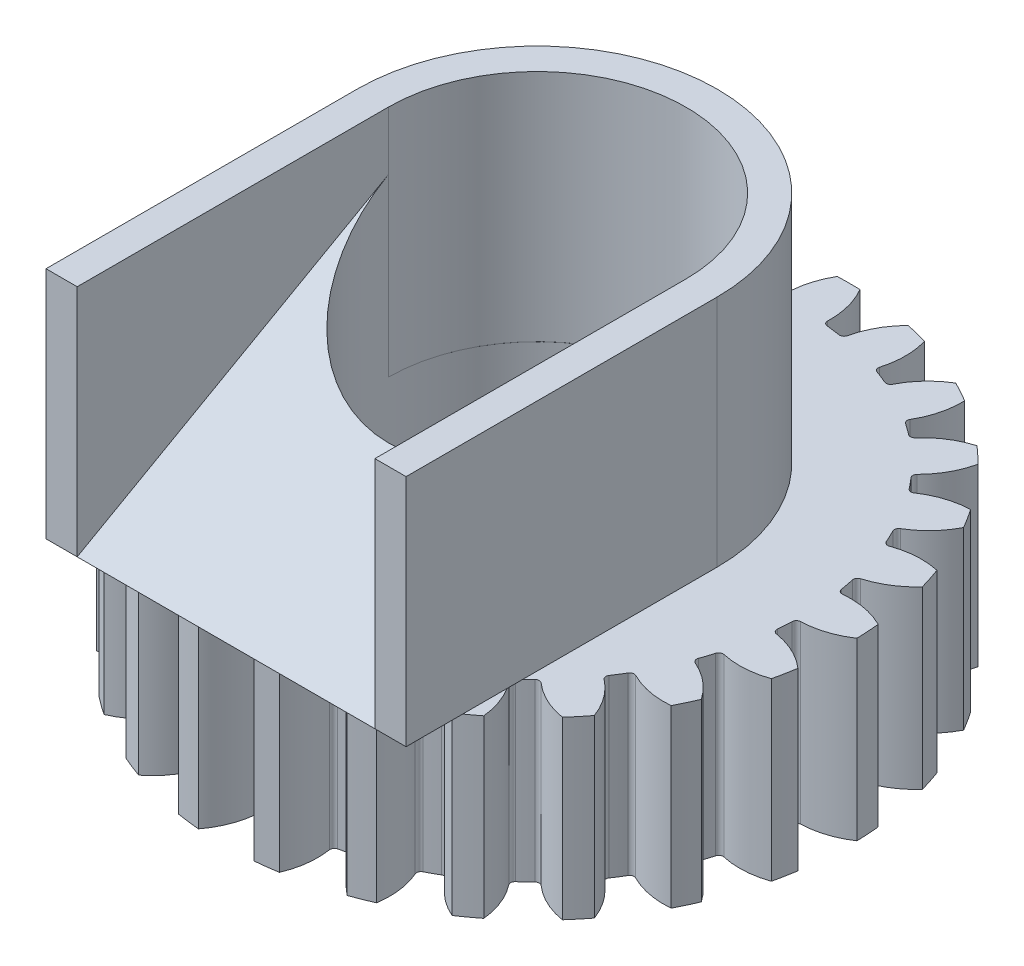
SolidWorks part; units mm, degrees
ref_plane "Front Plane" through (0, 0, 0) normal (0, 0, 1) x (1, 0, 0)
ref_plane "Top Plane" through (0, 0, 0) normal (0, 1, 0) x (1, 0, 0)
ref_plane "Right Plane" through (0, 0, 0) normal (1, 0, 0) x (0, 0, -1)
sketch "Sketch3" plane through (0, 0, 0) normal (0, 0, 1) x (1, 0, 0)
  line L0 (-0.0769, 25.8145) -> (20.8731, 25.8145)
  line L1 (20.8731, 25.8145) -> (20.8731, 3.3145)
  line L2 (20.8731, 3.3145) -> (-0.0769, 3.3145)
  line L5 (-0.0769, 3.3145) -> (-0.0769, 25.8145)
  line L6 (-19.1269, 24.9434) -> (-19.1269, -20.3377) construction
  dimension "D1" = 19.05
  dimension "D2" = 40
  dimension "D4" = 22.5
revolve "Revolve1" add sketch "Sketch3" angle 360 about L6
sketch "Sketch5" plane through (0, 3.3145, 0) normal (0, -1, 0) x (1, 0, 0)
  line L0 (-19.1269, 0) -> (-19.1269, 40) construction
  line L1 (-20.5562, 33.9699) -> (-19.1269, 0) construction
  line L2 (-19.1269, 31.4562) -> (-23.8282, 44.3728) construction
  arc A0 (-15.5608, 39.8407) -> (-22.693, 39.8407) centre (-19.1269, 0) ccw
  arc A1 (-17.1279, 36.946) -> (-21.1259, 36.946) centre (-19.1269, 0) ccw construction
  arc A2 (-17.6976, 33.9699) -> (-20.5562, 33.9699) centre (-19.1269, 0) ccw
  arc A3 (-22.693, 39.8407) -> (-20.5562, 33.9699) centre (-30.8833, 33.5354) cw
  arc A4 (-15.5608, 39.8407) -> (-17.6976, 33.9699) centre (-7.3705, 33.5354) ccw
  point P14 (-21.1704, 37.0706)
  dimension "D1" = 74
  dimension "D2" = 80
  dimension "D3" = 68
  dimension "D4" = 20
  dimension "D5" = 4
extrude "Cut-Extrude1" cut sketch "Sketch5" against normal through all
fillet "Fillet1" radius 0.57 2 edges at (-20.5562, 14.5645, 33.9699) (-17.6976, 14.5645, 33.9699)
pattern_circular "CirPattern1" count 25 over 360 about axis through (-19.1269, 25.8145, 0) along (0, 1, 0) of "Fillet1", "Cut-Extrude1"
sketch "Sketch6" plane through (0, 25.8145, 0) normal (0, 1, 0) x (1, 0, 0)
  line L0 (-42.1769, 0) -> (-42.1769, -39.9017)
  line L1 (-42.1769, -39.9017) -> (-38.1769, -39.9017)
  line L2 (-38.1769, -39.9017) -> (-38.1769, 0)
  line L3 (0, 0) -> (0, -39.9017)
  line L4 (0, -39.9017) -> (4, -39.9017)
  line L5 (4, -39.9017) -> (4, 0)
  arc A0 (-38.1769, 0) -> (0, 0) centre (-19.0885, 0) cw
  circle A1 centre (-19.1269, 0) radius 19.05 construction
  arc A2 (-42.1769, 0) -> (4, 0) centre (-19.0885, 0) cw
  dimension "D1" = 19.0885
  dimension "D2" = 4
  dimension "D3" = 4
extrude "Boss-Extrude1" add sketch "Sketch6" along normal blind 30
sketch "Sketch8" plane through (-38.1769, 0, 0) normal (1, 0, 0) x (0, 0, -1)
  line L2 (0, 25.8145) -> (-39.9017, 25.8145)
  line L3 (-39.9017, 25.8145) -> (0, 48.3145)
  line L4 (0, 48.3145) -> (0, 25.8145)
  line L5 (0, 55.8145) -> (0, 25.8145) construction
  dimension "D1" = 22.5
extrude "Boss-Extrude2" add sketch "Sketch8" along normal blind 39
sketch "Sketch9" plane through (0, 25.8145, 0) normal (0, -1, 0) x (-1, 0, 0)
  line L0 (0.0769, 0) -> (38.1769, 0) construction
  circle A0 centre (19.1269, 0) radius 19.05
extrude "Cut-Extrude2" cut sketch "Sketch9" against normal through all
